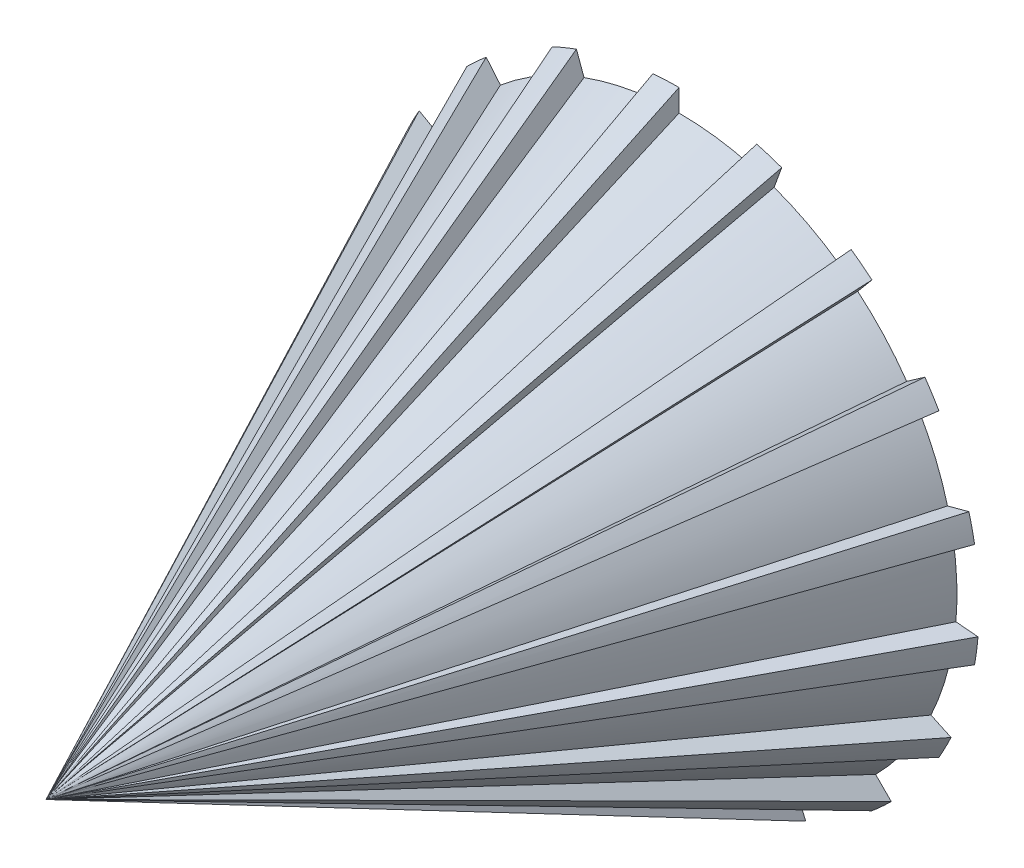
SolidWorks part; units mm, degrees
ref_plane "Front Plane" through (0, 0, 0) normal (0, 0, 1) x (1, 0, 0)
ref_plane "Top Plane" through (0, 0, 0) normal (0, 1, 0) x (1, 0, 0)
ref_plane "Right Plane" through (0, 0, 0) normal (1, 0, 0) x (0, 0, -1)
sketch "Sketch1" plane through (0, 0, 0) normal (0, 0, 1) x (1, 0, 0)
  line L0 (-5.4991, 5.1) -> (5.4991, 5.1)
  circle A0 centre (0, 0) radius 50
  circle A1 centre (0, 0) radius 15
  arc A2 (-5.4991, 5.1) -> (5.4991, 5.1) centre (0, 0) ccw
  circle A3 centre (0, 0) radius 50
  dimension "D1" = 15
  dimension "D2" = 30
  dimension "D3" = 100
  dimension "D4" = 5.1
extrude "Boss-Extrude1" add sketch "Sketch1" against normal blind 2 contours A1 A2 L0 region at (-14.5757, 0, 0)
ref_plane "Plane1" through (0, 0, 100) normal (0, 0, 1) x (1, 0, 0)
sketch "Sketch2" plane through (0, 0, 100) normal (0, 0, 1) x (1, 0, 0)
  point P0 (0, 0)
sketch "Sketch3" plane through (0, 0, 0) normal (0, 0, 1) x (1, 0, 0)
  line L0 (0, 0) -> (-15.0147, 41.2525) construction
  line L1 (0, 0) -> (0, 47.4) construction
  line L2 (0, 47.4) -> (0, 43.9)
  line L3 (-4.1312, 47.2196) -> (-3.8261, 43.7329)
  line L4 (12.268, 45.7849) -> (11.3622, 42.4041)
  line L5 (16.2118, 44.5414) -> (15.0147, 41.2525)
  line L6 (27.1875, 38.8278) -> (25.18, 35.9608)
  line L7 (30.4681, 36.3105) -> (28.2184, 33.6294)
  line L8 (38.8278, 27.1875) -> (35.9608, 25.18)
  line L9 (41.0496, 23.7) -> (38.0185, 21.95)
  line L10 (45.7849, 12.268) -> (42.4041, 11.3622)
  line L11 (46.6799, 8.2309) -> (43.2331, 7.6232)
  line L12 (47.2196, -4.1312) -> (43.7329, -3.8261)
  line L13 (46.6799, -8.2309) -> (43.2331, -7.6232)
  line L14 (42.959, -20.0321) -> (39.7869, -18.5529)
  line L15 (41.0496, -23.7) -> (38.0185, -21.95)
  line L16 (33.5169, -33.5169) -> (31.042, -31.042)
  line L17 (30.4681, -36.3105) -> (28.2184, -33.6294)
  line L18 (20.0321, -42.959) -> (18.5529, -39.7869)
  line L19 (16.2118, -44.5414) -> (15.0147, -41.2525)
  line L20 (4.1312, -47.2196) -> (3.8261, -43.7329)
  line L21 (0, -47.4) -> (0, -43.9)
  line L22 (-12.268, -45.7849) -> (-11.3622, -42.4041)
  line L23 (-16.2118, -44.5414) -> (-15.0147, -41.2525)
  line L24 (-27.1875, -38.8278) -> (-25.18, -35.9608)
  line L25 (-30.4681, -36.3105) -> (-28.2184, -33.6294)
  line L26 (-38.8278, -27.1875) -> (-35.9608, -25.18)
  line L27 (-41.0496, -23.7) -> (-38.0185, -21.95)
  line L28 (-45.7849, -12.268) -> (-42.4041, -11.3622)
  line L29 (-46.6799, -8.2309) -> (-43.2331, -7.6232)
  line L30 (-47.2196, 4.1312) -> (-43.7329, 3.8261)
  line L31 (-46.6799, 8.2309) -> (-43.2331, 7.6232)
  line L32 (-42.959, 20.0321) -> (-39.7869, 18.5529)
  line L33 (-41.0496, 23.7) -> (-38.0185, 21.95)
  line L34 (-33.5169, 33.5169) -> (-31.042, 31.042)
  line L35 (-30.4681, 36.3105) -> (-28.2184, 33.6294)
  line L36 (-20.0321, 42.959) -> (-18.5529, 39.7869)
  line L37 (-16.2118, 44.5414) -> (-15.0147, 41.2525)
  arc A0 (0, 47.4) -> (-4.1312, 47.2196) centre (0, 0) ccw
  arc A1 (-3.8261, 43.7329) -> (-15.0147, 41.2525) centre (0, 0) ccw
  arc A2 (11.3622, 42.4041) -> (0, 43.9) centre (0, 0) ccw
  arc A3 (16.2118, 44.5414) -> (12.268, 45.7849) centre (0, 0) ccw
  arc A4 (25.18, 35.9608) -> (15.0147, 41.2525) centre (0, 0) ccw
  arc A5 (30.4681, 36.3105) -> (27.1875, 38.8278) centre (0, 0) ccw
  arc A6 (35.9608, 25.18) -> (28.2184, 33.6294) centre (0, 0) ccw
  arc A7 (41.0496, 23.7) -> (38.8278, 27.1875) centre (0, 0) ccw
  arc A8 (42.4041, 11.3622) -> (38.0185, 21.95) centre (0, 0) ccw
  arc A9 (46.6799, 8.2309) -> (45.7849, 12.268) centre (0, 0) ccw
  arc A10 (43.7329, -3.8261) -> (43.2331, 7.6232) centre (0, 0) ccw
  arc A11 (46.6799, -8.2309) -> (47.2196, -4.1312) centre (0, 0) ccw
  arc A12 (39.7869, -18.5529) -> (43.2331, -7.6232) centre (0, 0) ccw
  arc A13 (41.0496, -23.7) -> (42.959, -20.0321) centre (0, 0) ccw
  arc A14 (31.042, -31.042) -> (38.0185, -21.95) centre (0, 0) ccw
  arc A15 (30.4681, -36.3105) -> (33.5169, -33.5169) centre (0, 0) ccw
  arc A16 (18.5529, -39.7869) -> (28.2184, -33.6294) centre (0, 0) ccw
  arc A17 (16.2118, -44.5414) -> (20.0321, -42.959) centre (0, 0) ccw
  arc A18 (3.8261, -43.7329) -> (15.0147, -41.2525) centre (0, 0) ccw
  arc A19 (0, -47.4) -> (4.1312, -47.2196) centre (0, 0) ccw
  arc A20 (-11.3622, -42.4041) -> (0, -43.9) centre (0, 0) ccw
  arc A21 (-16.2118, -44.5414) -> (-12.268, -45.7849) centre (0, 0) ccw
  arc A22 (-25.18, -35.9608) -> (-15.0147, -41.2525) centre (0, 0) ccw
  arc A23 (-30.4681, -36.3105) -> (-27.1875, -38.8278) centre (0, 0) ccw
  arc A24 (-35.9608, -25.18) -> (-28.2184, -33.6294) centre (0, 0) ccw
  arc A25 (-41.0496, -23.7) -> (-38.8278, -27.1875) centre (0, 0) ccw
  arc A26 (-42.4041, -11.3622) -> (-38.0185, -21.95) centre (0, 0) ccw
  arc A27 (-46.6799, -8.2309) -> (-45.7849, -12.268) centre (0, 0) ccw
  arc A28 (-43.7329, 3.8261) -> (-43.2331, -7.6232) centre (0, 0) ccw
  arc A29 (-46.6799, 8.2309) -> (-47.2196, 4.1312) centre (0, 0) ccw
  arc A30 (-39.7869, 18.5529) -> (-43.2331, 7.6232) centre (0, 0) ccw
  arc A31 (-41.0496, 23.7) -> (-42.959, 20.0321) centre (0, 0) ccw
  arc A32 (-31.042, 31.042) -> (-38.0185, 21.95) centre (0, 0) ccw
  arc A33 (-30.4681, 36.3105) -> (-33.5169, 33.5169) centre (0, 0) ccw
  arc A34 (-18.5529, 39.7869) -> (-28.2184, 33.6294) centre (0, 0) ccw
  arc A35 (-16.2118, 44.5414) -> (-20.0321, 42.959) centre (0, 0) ccw
  point P3 (0, 0)
  point P9 (-61.2008, 41.9803)
  dimension "D1" = 47.4
  dimension "D2" = 3.5
  dimension "D3" = 5
  dimension "D4" = 18
loft "Loft2" add profiles "Sketch3", "Sketch2"
extrude "Cut-Extrude1" cut sketch "Sketch1<4>" along normal blind 10 contours L0 A2 region at (0, -0.6996, 0)
sketch "Sketch1<4>" plane through (0, 0, 0) normal (0, 0, 1) x (1, 0, 0) same geometry as "Sketch1"
